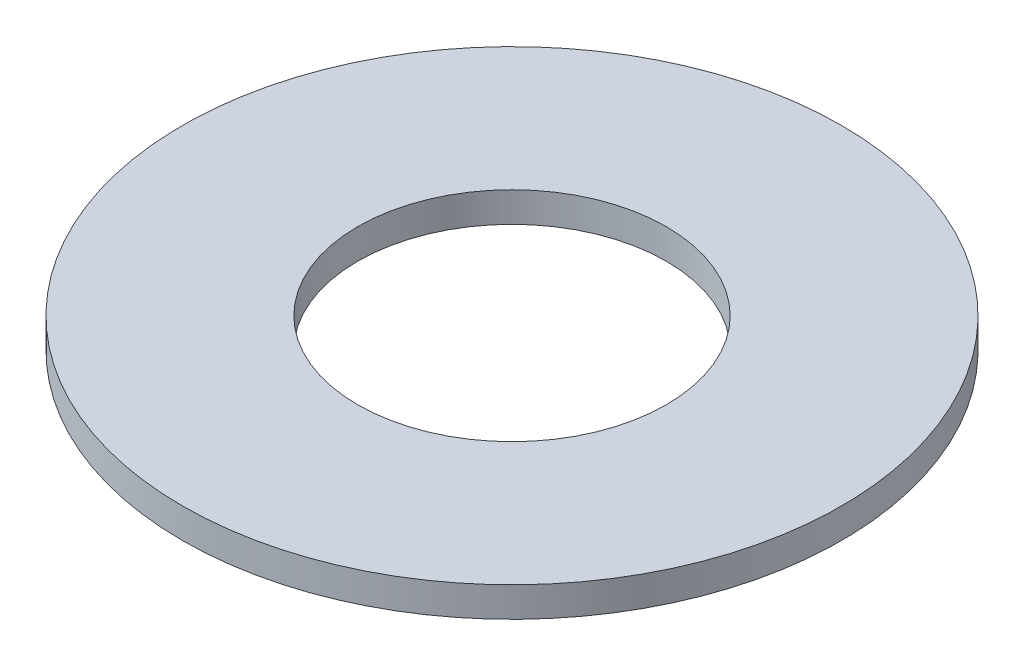
SolidWorks part; units mm, degrees
material "6061-T6 (SS)"
ref_plane "Front Plane" through (0, 0, 0) normal (0, 0, 1) x (1, 0, 0)
ref_plane "Top Plane" through (0, 0, 0) normal (0, 1, 0) x (1, 0, 0)
ref_plane "Right Plane" through (0, 0, 0) normal (1, 0, 0) x (0, 0, -1)
sketch "Sketch1" plane through (0, 0, 0) normal (0, 1, 0) x (1, 0, 0)
  circle A0 centre (0, 0) radius 5.15
  circle A1 centre (0, 0) radius 11
  dimension "D1" = 10.3
  dimension "D2" = 22
extrude "Boss-Extrude1" add sketch "Sketch1" along normal blind 1
